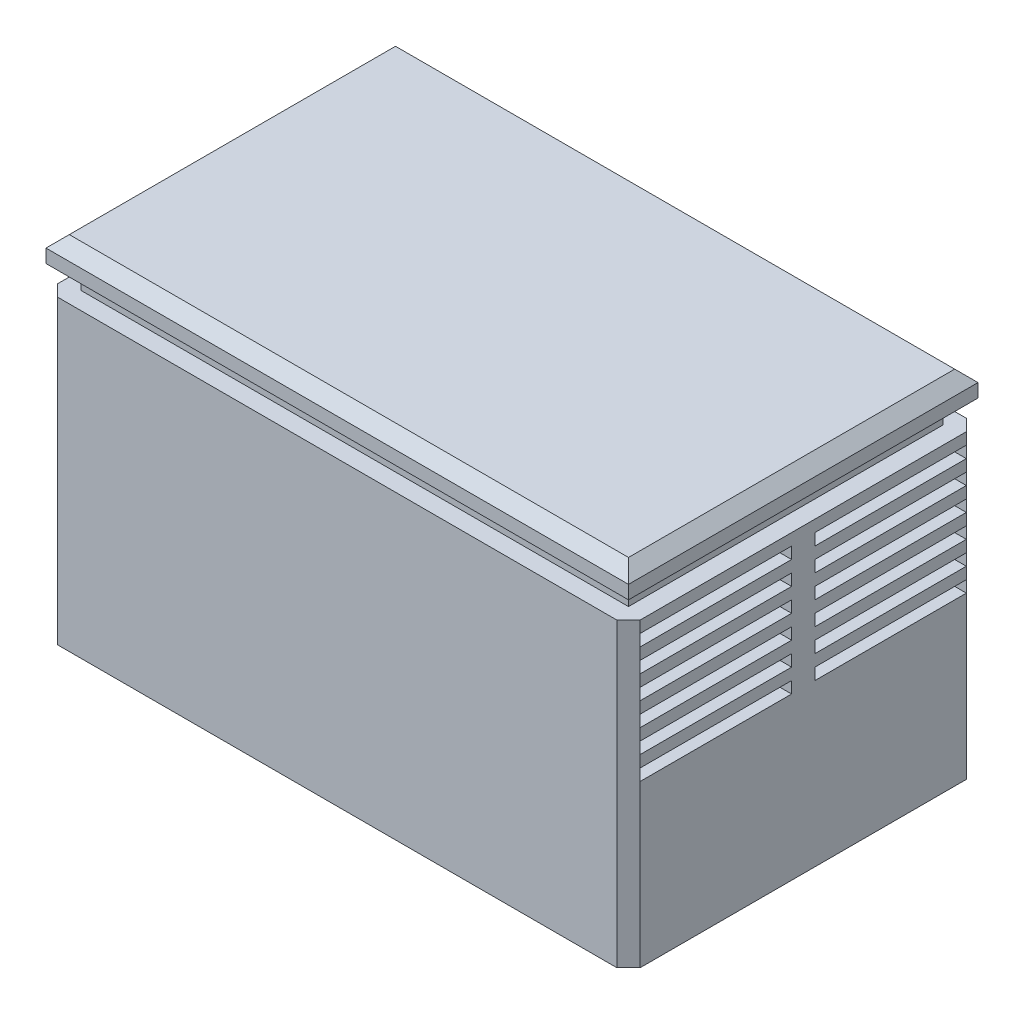
SolidWorks part; units mm, degrees
material "2024 Alloy"
ref_plane "Front Plane" through (0, 0, 0) normal (0, 0, 1) x (1, 0, 0)
ref_plane "Top Plane" through (0, 0, 0) normal (0, 1, 0) x (1, 0, 0)
ref_plane "Right Plane" through (0, 0, 0) normal (1, 0, 0) x (0, 0, -1)
sketch "Sketch1" plane through (0, 0, 0) normal (0, 0, 1) x (1, 0, 0)
  line L0 (250, 118.4806) -> (235, 118.4806)
  line L1 (250, 150) -> (-250, 150)
  line L2 (250, 150) -> (250, 118.4806)
  line L3 (250, -150) -> (-250, -150)
  line L4 (-250, 150) -> (-250, 118.4806)
  line L5 (250, 150) -> (-250, -150) construction
  line L6 (250, -150) -> (-250, 150) construction
  line L7 (235, 118.4806) -> (235, 108.4806)
  line L8 (235, 108.4806) -> (250, 108.4806)
  line L9 (-250, 118.4806) -> (-235, 118.4806)
  line L10 (-235, 118.4806) -> (-235, 108.4806)
  line L11 (-235, 108.4806) -> (-250, 108.4806)
  line L12 (250, 108.4806) -> (250, -150)
  line L13 (-250, 108.4806) -> (-250, -150)
  point P0 (0, 0)
  dimension "D1" = 500
  dimension "D2" = 300
  dimension "D3" = 10
  dimension "D4" = 15
  dimension "D5" = 15
  dimension "D6" = 10
extrude "Boss-Extrude1" add sketch "Sketch1" along normal blind 300
sketch "Sketch2" plane through (-250, 0, 0) normal (-1, 0, 0) x (0, 0, 1)
  line L0 (300, 108.4806) -> (0, 108.4806) construction
  line L1 (300, 118.4806) -> (285, 118.4806)
  line L2 (300, 118.4806) -> (300, 108.4806)
  line L3 (300, 108.4806) -> (285, 108.4806)
  line L4 (285, 118.4806) -> (285, 108.4806)
  line L6 (0, 118.4806) -> (15, 118.4806)
  line L7 (0, 118.4806) -> (0, 108.4806)
  line L8 (0, 108.4806) -> (15, 108.4806)
  line L9 (15, 118.4806) -> (15, 108.4806)
  dimension "D1" = 15
  dimension "D2" = 15
extrude "Cut-Extrude1" cut sketch "Sketch2" against normal through all
sketch "Sketch4" plane through (-250, 0, 0) normal (-1, 0, 0) x (0, 0, 1)
  line L10 (0, 108.4806) -> (0, -150) construction
  line L11 (10, 98.4806) -> (140, 98.4806)
  line L12 (10, 98.4806) -> (10, 88.4806)
  line L13 (10, 88.4806) -> (140, 88.4806)
  line L14 (140, 98.4806) -> (140, 88.4806)
  line L15 (300, 108.4806) -> (0, 108.4806) construction
  line L16 (160, 98.4806) -> (160, 88.4806)
  line L17 (160, 88.4806) -> (290, 88.4806)
  line L18 (160, 98.4806) -> (290, 98.4806)
  line L19 (290, 98.4806) -> (290, 88.4806)
  line L20 (160, 78.4806) -> (160, 68.4806)
  line L21 (160, 68.4806) -> (290, 68.4806)
  line L22 (160, 78.4806) -> (290, 78.4806)
  line L23 (290, 78.4806) -> (290, 68.4806)
  line L24 (160, 58.4806) -> (160, 48.4806)
  line L25 (160, 48.4806) -> (290, 48.4806)
  line L26 (160, 58.4806) -> (290, 58.4806)
  line L27 (290, 58.4806) -> (290, 48.4806)
  line L28 (160, 38.4806) -> (160, 28.4806)
  line L29 (160, 28.4806) -> (290, 28.4806)
  line L30 (160, 38.4806) -> (290, 38.4806)
  line L31 (290, 38.4806) -> (290, 28.4806)
  line L32 (160, 18.4806) -> (160, 8.4806)
  line L33 (160, 8.4806) -> (290, 8.4806)
  line L34 (160, 18.4806) -> (290, 18.4806)
  line L35 (290, 18.4806) -> (290, 8.4806)
  line L36 (160, -1.5194) -> (160, -11.5194)
  line L37 (160, -11.5194) -> (290, -11.5194)
  line L38 (160, -1.5194) -> (290, -1.5194)
  line L39 (290, -1.5194) -> (290, -11.5194)
  line L40 (10, 78.4806) -> (10, 68.4806)
  line L41 (10, 68.4806) -> (140, 68.4806)
  line L42 (10, 78.4806) -> (140, 78.4806)
  line L43 (140, 78.4806) -> (140, 68.4806)
  line L44 (10, 58.4806) -> (10, 48.4806)
  line L45 (10, 48.4806) -> (140, 48.4806)
  line L46 (10, 58.4806) -> (140, 58.4806)
  line L47 (140, 58.4806) -> (140, 48.4806)
  line L48 (10, 38.4806) -> (10, 28.4806)
  line L49 (10, 28.4806) -> (140, 28.4806)
  line L50 (10, 38.4806) -> (140, 38.4806)
  line L51 (140, 38.4806) -> (140, 28.4806)
  line L52 (10, 18.4806) -> (10, 8.4806)
  line L53 (10, 8.4806) -> (140, 8.4806)
  line L54 (10, 18.4806) -> (140, 18.4806)
  line L55 (140, 18.4806) -> (140, 8.4806)
  line L56 (10, -1.5194) -> (10, -11.5194)
  line L57 (10, -11.5194) -> (140, -11.5194)
  line L58 (10, -1.5194) -> (140, -1.5194)
  line L59 (140, -1.5194) -> (140, -11.5194)
  dimension "D1" = 10
  dimension "D2" = 10
  dimension "D3" = 10
  dimension "D4" = 130
  dimension "D5" = 2
  dimension "D6" = 6
extrude "Cut-Extrude2" cut sketch "Sketch4" against normal blind 30
sketch "Sketch7" plane through (250, 0, 0) normal (1, 0, 0) x (0, 0, -1)
  line L0 (-300, -150) -> (-300, 108.4806) construction
  line L1 (-290, 98.4806) -> (-160, 98.4806)
  line L2 (-290, 98.4806) -> (-290, 88.4806)
  line L3 (-290, 88.4806) -> (-160, 88.4806)
  line L4 (-160, 98.4806) -> (-160, 88.4806)
  line L5 (-285, 108.4806) -> (-15, 108.4806) construction
  line L6 (-140, 98.4806) -> (-140, 88.4806)
  line L7 (-140, 98.4806) -> (-10, 98.4806)
  line L8 (-140, 88.4806) -> (-10, 88.4806)
  line L9 (-10, 98.4806) -> (-10, 88.4806)
  line L10 (-140, 78.4806) -> (-140, 68.4806)
  line L11 (-140, 78.4806) -> (-10, 78.4806)
  line L12 (-140, 68.4806) -> (-10, 68.4806)
  line L13 (-10, 78.4806) -> (-10, 68.4806)
  line L14 (-140, 58.4806) -> (-140, 48.4806)
  line L15 (-140, 58.4806) -> (-10, 58.4806)
  line L16 (-140, 48.4806) -> (-10, 48.4806)
  line L17 (-10, 58.4806) -> (-10, 48.4806)
  line L18 (-140, 38.4806) -> (-140, 28.4806)
  line L19 (-140, 38.4806) -> (-10, 38.4806)
  line L20 (-140, 28.4806) -> (-10, 28.4806)
  line L21 (-10, 38.4806) -> (-10, 28.4806)
  line L22 (-140, 18.4806) -> (-140, 8.4806)
  line L23 (-140, 18.4806) -> (-10, 18.4806)
  line L24 (-140, 8.4806) -> (-10, 8.4806)
  line L25 (-10, 18.4806) -> (-10, 8.4806)
  line L26 (-140, -1.5194) -> (-140, -11.5194)
  line L27 (-140, -1.5194) -> (-10, -1.5194)
  line L28 (-140, -11.5194) -> (-10, -11.5194)
  line L29 (-10, -1.5194) -> (-10, -11.5194)
  line L30 (-290, 78.4806) -> (-290, 68.4806)
  line L31 (-290, 78.4806) -> (-160, 78.4806)
  line L32 (-290, 68.4806) -> (-160, 68.4806)
  line L33 (-160, 78.4806) -> (-160, 68.4806)
  line L34 (-290, 58.4806) -> (-290, 48.4806)
  line L35 (-290, 58.4806) -> (-160, 58.4806)
  line L36 (-290, 48.4806) -> (-160, 48.4806)
  line L37 (-160, 58.4806) -> (-160, 48.4806)
  line L38 (-290, 38.4806) -> (-290, 28.4806)
  line L39 (-290, 38.4806) -> (-160, 38.4806)
  line L40 (-290, 28.4806) -> (-160, 28.4806)
  line L41 (-160, 38.4806) -> (-160, 28.4806)
  line L42 (-290, 18.4806) -> (-290, 8.4806)
  line L43 (-290, 18.4806) -> (-160, 18.4806)
  line L44 (-290, 8.4806) -> (-160, 8.4806)
  line L45 (-160, 18.4806) -> (-160, 8.4806)
  line L46 (-290, -1.5194) -> (-290, -11.5194)
  line L47 (-290, -1.5194) -> (-160, -1.5194)
  line L48 (-290, -11.5194) -> (-160, -11.5194)
  line L49 (-160, -1.5194) -> (-160, -11.5194)
  dimension "D1" = 10
  dimension "D2" = 10
  dimension "D3" = 10
  dimension "D4" = 130
  dimension "D5" = 2
  dimension "D6" = 6
extrude "Cut-Extrude3" cut sketch "Sketch7" against normal blind 30
chamfer "Chamfer1" distance 10 angle 45 4 edges at (250, 150, 150) (0, 150, 300) (-250, 150, 150) (0, 150, 0)
chamfer "Chamfer2" distance 10 angle 45 4 edges at (250, 118.4806, 150) (0, 118.4806, 300) (0, 118.4806, 0) (-250, 118.4806, 150)
chamfer "Chamfer3" distance 10 angle 45 4 edges at (250, -20.7597, 300) (250, -20.7597, 0) (-250, -20.7597, 0) (-250, -20.7597, 300)
sketch "Sketch8" plane through (0, -150, 0) normal (0, -1, 0) x (1, 0, 0)
  line L1 (0, 35) -> (-215, 35) construction
  line L2 (0, 35) -> (0, 265) construction
  line L3 (0, 265) -> (-215, 265) construction
  line L4 (-215, 35) -> (-215, 265) construction
  line L5 (-240, 0) -> (240, 0) construction
  line L7 (-240, 300) -> (240, 300) construction
  line L8 (-250, 290) -> (-250, 10) construction
  circle A0 centre (-215, 35) radius 5
  circle A1 centre (-215, 265) radius 5
  circle A2 centre (0, 265) radius 5
  circle A3 centre (0, 35) radius 5
  dimension "D4" = 10
  dimension "D1" = 35
  dimension "D2" = 35
  dimension "D3" = 35
extrude "Cut-Extrude4" cut sketch "Sketch8" against normal blind 30
